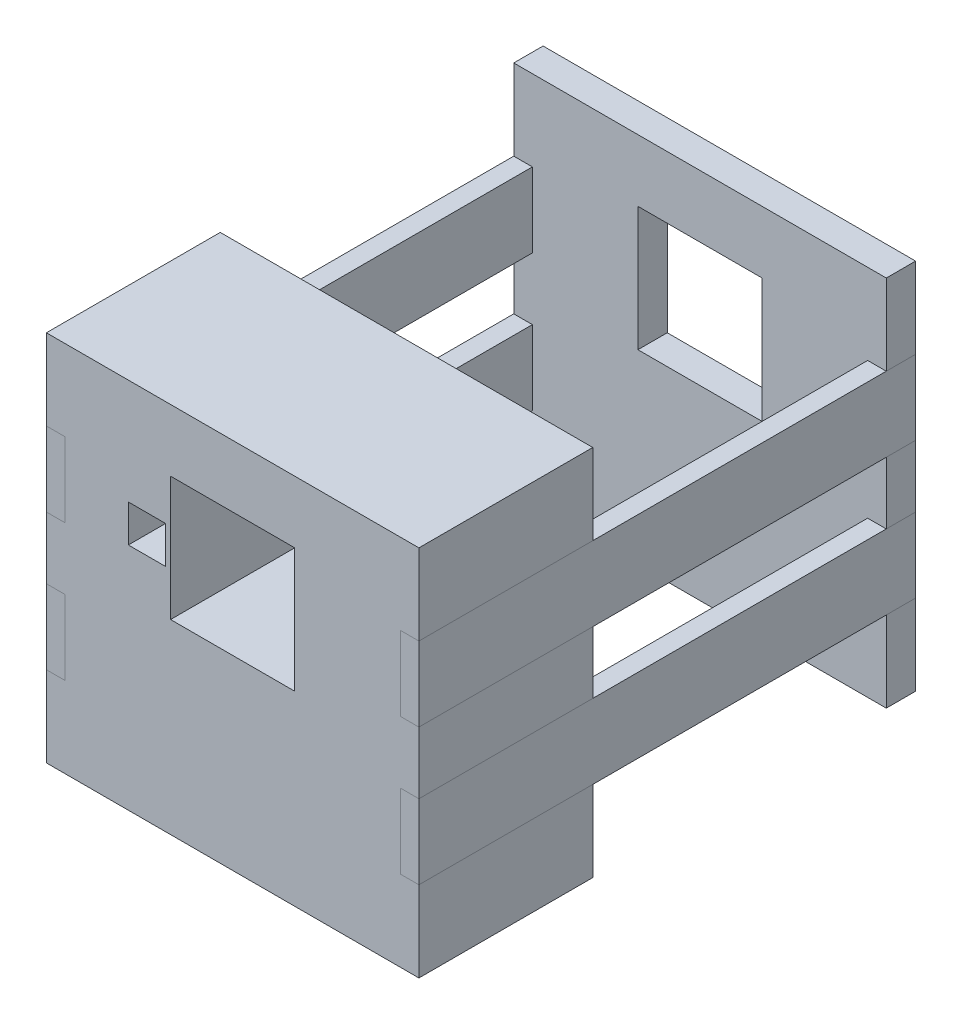
SolidWorks part; units mm, degrees
ref_plane "Front Plane" through (0, 0, 0) normal (0, 0, 1) x (1, 0, 0)
ref_plane "Top Plane" through (0, 0, 0) normal (0, 1, 0) x (1, 0, 0)
ref_plane "Right Plane" through (0, 0, 0) normal (1, 0, 0) x (0, 0, -1)
sketch "Sketch1" plane through (0, 0, 0) normal (0, 0, 1) x (1, 0, 0)
  line L1 (0, 0) -> (38.1, 0)
  line L2 (0, 0) -> (0, 38.1)
  line L3 (0, 38.1) -> (38.1, 38.1)
  line L4 (38.1, 0) -> (38.1, 38.1)
  dimension "D1" = 38.1
  dimension "box" = 38.1
extrude "Boss-Extrude1" add sketch "Sketch1" against normal blind 17.78
sketch "Sketch2" plane through (0, 0, 0) normal (0, 0, 1) x (1, 0, 0)
  line L0 (0, 19.05) -> (38.1, 19.05) construction
  line L1 (0, 0) -> (0, 38.1) construction
  line L2 (38.1, 0) -> (38.1, 38.1) construction
  line L3 (19.05, 0) -> (19.05, 38.1) construction
  line L4 (0, 0) -> (38.1, 0) construction
  line L5 (0, 38.1) -> (38.1, 38.1) construction
  line L6 (38.1, 22.225) -> (36.195, 22.225)
  line L7 (12.7, 31.75) -> (25.4, 31.75)
  line L8 (12.7, 31.75) -> (12.7, 19.05)
  line L9 (12.7, 19.05) -> (25.4, 19.05)
  line L10 (25.4, 31.75) -> (25.4, 19.05)
  line L11 (0, 29.845) -> (1.905, 29.845)
  line L12 (0, 29.845) -> (0, 22.225)
  line L13 (0, 22.225) -> (1.905, 22.225)
  line L14 (1.905, 29.845) -> (1.905, 22.225)
  line L15 (36.195, 29.845) -> (36.195, 22.225)
  line L16 (38.1, 29.845) -> (36.195, 29.845)
  line L17 (38.1, 29.845) -> (38.1, 22.225)
  line L18 (38.1, 8.255) -> (38.1, 15.875)
  line L19 (38.1, 8.255) -> (36.195, 8.255)
  line L20 (36.195, 8.255) -> (36.195, 15.875)
  line L21 (38.1, 15.875) -> (36.195, 15.875)
  line L22 (0, 15.875) -> (1.905, 15.875)
  line L23 (1.905, 8.255) -> (1.905, 15.875)
  line L24 (0, 8.255) -> (1.905, 8.255)
  line L25 (0, 8.255) -> (0, 15.875)
  line L27 (12.192, 27.305) -> (8.382, 27.305)
  line L28 (12.192, 27.305) -> (12.192, 23.495)
  line L29 (12.192, 23.495) -> (8.382, 23.495)
  line L30 (8.382, 27.305) -> (8.382, 23.495)
  point P36 (12.192, 25.4)
  dimension "D1" = 12.7
  dimension "D2" = 12.7
  dimension "D3" = 12.7
  dimension "D4" = 12.7
  dimension "D5" = 3.175
  dimension "D6" = 7.62
  dimension "D7" = 1.905
  dimension "D8" = 3.81
  dimension "D9" = 0.508
  dimension "D10" = 3.81
  dimension "D11" = 4.445
extrude "Cut-Extrude1" cut sketch "Sketch2" against normal blind 20.32
ref_plane "Plane1" through (0, 0, -50.8) normal (0, 0, 1) x (1, 0, 0)
sketch "Sketch3" plane through (0, 0, -50.8) normal (0, 0, 1) x (1, 0, 0)
  line L0 (12.7, 19.05) -> (25.4, 19.05) construction
  line L1 (25.4, 19.05) -> (25.4, 31.75) construction
  line L2 (25.4, 31.75) -> (12.7, 31.75) construction
  line L3 (12.7, 31.75) -> (12.7, 19.05) construction
  line L4 (12.7, 19.05) -> (25.4, 19.05)
  line L5 (25.4, 19.05) -> (25.4, 31.75)
  line L6 (25.4, 31.75) -> (12.7, 31.75)
  line L7 (12.7, 31.75) -> (12.7, 19.05)
  line L20 (38.1, 15.875) -> (38.1, 22.225)
  line L21 (38.1, 22.225) -> (36.195, 22.225)
  line L22 (36.195, 22.225) -> (36.195, 29.845)
  line L23 (36.195, 29.845) -> (38.1, 29.845)
  line L24 (38.1, 29.845) -> (38.1, 38.1)
  line L25 (38.1, 38.1) -> (0, 38.1)
  line L26 (0, 38.1) -> (0, 29.845)
  line L27 (0, 29.845) -> (1.905, 29.845)
  line L28 (1.905, 29.845) -> (1.905, 22.225)
  line L29 (1.905, 22.225) -> (0, 22.225)
  line L30 (0, 22.225) -> (0, 15.875)
  line L31 (0, 15.875) -> (1.905, 15.875)
  line L32 (1.905, 15.875) -> (1.905, 8.255)
  line L33 (1.905, 8.255) -> (0, 8.255)
  line L34 (0, 8.255) -> (0, 0)
  line L35 (0, 0) -> (38.1, 0)
  line L36 (38.1, 0) -> (38.1, 8.255)
  line L37 (38.1, 8.255) -> (36.195, 8.255)
  line L38 (36.195, 8.255) -> (36.195, 15.875)
  line L39 (36.195, 15.875) -> (38.1, 15.875)
  line L40 (38.1, 15.875) -> (38.1, 22.225)
  line L41 (38.1, 22.225) -> (36.195, 22.225)
  line L42 (36.195, 22.225) -> (36.195, 29.845)
  line L43 (36.195, 29.845) -> (38.1, 29.845)
  line L44 (38.1, 29.845) -> (38.1, 38.1)
  line L45 (38.1, 38.1) -> (0, 38.1)
  line L46 (0, 38.1) -> (0, 29.845)
  line L47 (0, 29.845) -> (1.905, 29.845)
  line L48 (1.905, 29.845) -> (1.905, 22.225)
  line L49 (1.905, 22.225) -> (0, 22.225)
  line L50 (0, 22.225) -> (0, 15.875)
  line L51 (0, 15.875) -> (1.905, 15.875)
  line L52 (1.905, 15.875) -> (1.905, 8.255)
  line L53 (1.905, 8.255) -> (0, 8.255)
  line L54 (0, 8.255) -> (0, 0)
  line L55 (0, 0) -> (38.1, 0)
  line L56 (38.1, 0) -> (38.1, 8.255)
  line L57 (38.1, 8.255) -> (36.195, 8.255)
  line L58 (36.195, 8.255) -> (36.195, 15.875)
  line L59 (36.195, 15.875) -> (38.1, 15.875)
  dimension "D1" = 0
extrude "Boss-Extrude2" add sketch "Sketch3" along normal blind 3 separate body
sketch "Sketch6" plane through (1.905, 0, 0) normal (-1, 0, 0) x (0, 0, 1)
  line L0 (-17.78, 29.845) -> (-17.78, 22.225) construction
  line L1 (-17.78, 38.1) -> (0, 38.1) construction
  circle A0 centre (-8.89, 27.2143) radius 1.27
  dimension "D2" = 2.54
  dimension "D1" = 8.89
  dimension "D3" = 10.8857
extrude "SpringPlunger Hole" cut sketch "Sketch6" against normal blind 3 contours A0
sketch "Sketch8" plane through (0, 0, 0) normal (0, 0, 1) x (1, 0, 0)
  line L0 (38.1, 0) -> (38.1, 38.1) construction
  line L1 (36.195, 22.225) -> (38.1, 22.225) construction
  line L2 (38.1, 29.845) -> (36.195, 29.845) construction
  line L3 (36.195, 29.845) -> (36.195, 22.225) construction
  line L4 (36.195, 8.255) -> (38.1, 8.255) construction
  line L5 (38.1, 15.875) -> (36.195, 15.875) construction
  line L6 (36.195, 15.875) -> (36.195, 8.255) construction
  line L7 (0, 8.255) -> (1.905, 8.255) construction
  line L8 (1.905, 8.255) -> (1.905, 15.875) construction
  line L9 (1.905, 15.875) -> (0, 15.875) construction
  line L10 (0, 22.225) -> (1.905, 22.225) construction
  line L11 (1.905, 22.225) -> (1.905, 29.845) construction
  line L12 (1.905, 29.845) -> (0, 29.845) construction
  line L13 (0, 0) -> (0, 38.1) construction
  line L14 (38.1, 8.255) -> (38.1, 15.875)
  line L15 (36.195, 22.225) -> (38.1, 22.225)
  line L16 (38.1, 29.845) -> (36.195, 29.845)
  line L17 (36.195, 29.845) -> (36.195, 22.225)
  line L18 (36.195, 8.255) -> (38.1, 8.255)
  line L19 (38.1, 15.875) -> (36.195, 15.875)
  line L20 (36.195, 15.875) -> (36.195, 8.255)
  line L21 (0, 8.255) -> (1.905, 8.255)
  line L22 (1.905, 8.255) -> (1.905, 15.875)
  line L23 (1.905, 15.875) -> (0, 15.875)
  line L24 (0, 22.225) -> (1.905, 22.225)
  line L25 (1.905, 22.225) -> (1.905, 29.845)
  line L26 (1.905, 29.845) -> (0, 29.845)
  line L27 (0, 8.255) -> (0, 15.875)
  line L28 (0, 22.225) -> (0, 29.845)
  line L29 (38.1, 22.225) -> (38.1, 29.845)
  point P6 (0, 17.9288)
  point P12 (0, 3.9034)
extrude "Support" add sketch "Sketch8" against normal up to surface (50.8 mm away) contours L26 L28 L24 L25 | L21 L22 L23 L27 | L16 L17 L15 L29 | L14 L19 L20 L18 up to face at (19.05, 19.05, -50.8)
equation "\"box\" = 1.5"
equation "\"D1@Sketch1\"=\"box\""
equation "\"shaft\" = 0.5"
equation "\"D1@Sketch2\"=\"shaft\""
equation "\"D2@Sketch2\"=\"shaft\""
equation "\"D4@Sketch2\"=\"shaft\""
equation "\"D3@Sketch2\"=(\"box\"-\"shaft\")/2"
equation "\"D5@Sketch2\"=\"shaft\"/4"
equation "\"D6@Sketch2\"=\"box\"*0.2"
equation "\"D7@Sketch2\"=\"D6@Sketch2\"/4"
equation "\"springHole\"=0.15"
equation "\"D8@Sketch2\"=\"springHole\""
equation "\"D10@Sketch2\"=\"D8@Sketch2\""
equation "\"D11@Sketch2\"=\"D2@Sketch2\"/2-\"D8@Sketch2\"/2"
equation "\"depth1\"=0.7"
equation "\"D1@Boss-Extrude1\"=\"depth1\""
equation "\"D1@Sketch6\"=\"depth1\"/2"
equation "\"springPinDiameter\"=0.1"
equation "\"D2@Sketch6\"=\"springPinDiameter\""
equation "\"D3@Sketch6\"=\"box\"/3.5"
